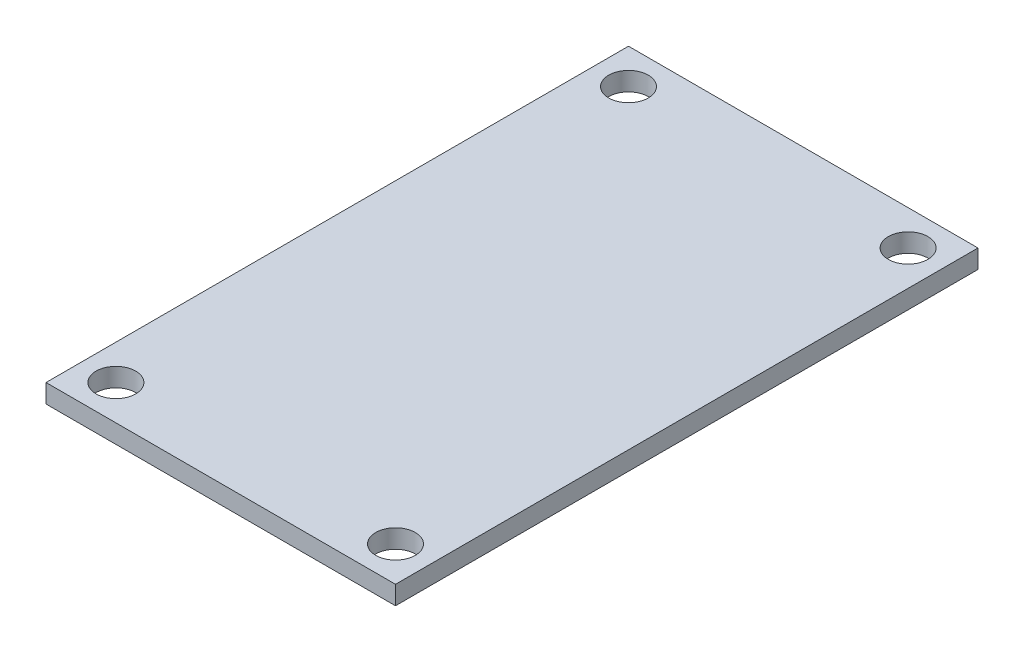
SolidWorks part; units mm, degrees
ref_plane "Front Plane" through (0, 0, 0) normal (0, 0, 1) x (1, 0, 0)
ref_plane "Top Plane" through (0, 0, 0) normal (0, 1, 0) x (1, 0, 0)
ref_plane "Right Plane" through (0, 0, 0) normal (1, 0, 0) x (0, 0, -1)
sketch "Sketch1" plane through (0, 0, 0) normal (0, 1, 0) x (1, 0, 0)
  line L0 (3, 47) -> (0, 47) construction
  line L1 (0, 0) -> (30, 0)
  line L2 (0, 0) -> (0, 50)
  line L3 (0, 50) -> (30, 50)
  line L4 (30, 0) -> (30, 50)
  line L5 (3, 47) -> (27, 47) construction
  line L6 (3, 47) -> (3, 3) construction
  line L7 (3, 3) -> (27, 3) construction
  line L8 (27, 47) -> (27, 3) construction
  line L9 (3, 47) -> (3, 50) construction
  line L10 (27, 3) -> (27, 0) construction
  line L11 (27, 3) -> (30, 3) construction
  circle A0 centre (3, 3) radius 1.7
  circle A1 centre (27, 3) radius 1.7
  circle A2 centre (3, 47) radius 1.7
  circle A3 centre (27, 47) radius 1.7
  dimension "D1" = 3.4
  dimension "D2" = 30
  dimension "D3" = 50
  dimension "D4" = 3
extrude "Boss-Extrude1" add sketch "Sketch1" along normal blind 1.6
